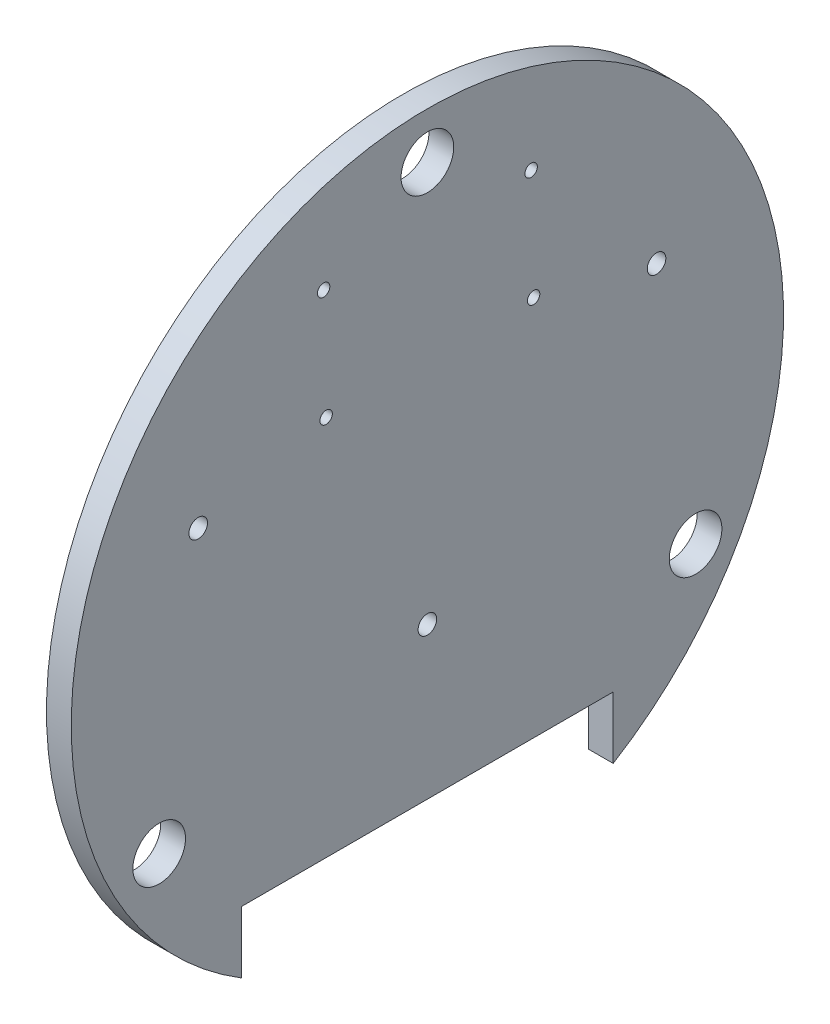
SolidWorks part; units mm, degrees
ref_plane "Ebene vorne" through (0, 0, 0) normal (0, 0, 1) x (1, 0, 0)
ref_plane "Ebene oben" through (0, 0, 0) normal (0, 1, 0) x (1, 0, 0)
ref_plane "Ebene rechts" through (0, 0, 0) normal (1, 0, 0) x (0, 0, -1)
sketch "Sketch1" plane through (0, 0, 0) normal (1, 0, 0) x (0, 0, -1)
  circle A0 centre (0, 0) radius 57.5
  dimension "D1" = 115
extrude "Boss-Extrude1" add sketch "Sketch1" along normal blind 4
sketch "Sketch2" plane through (0, 0, 0) normal (-1, 0, 0) x (0, 0, 1)
  circle A0 centre (0, 50) radius 4.25
  circle A1 centre (43.3013, -25) radius 4.25
  circle A2 centre (-43.3013, -25) radius 4.25
  point P9 (0, 0)
  dimension "D1" = 8.5
  dimension "D2" = 50
  dimension "D3" = 3
extrude "Cut-Extrude1" cut sketch "Sketch2" against normal through all
sketch "Sketch3" plane through (0, 0, 0) normal (-1, 0, 0) x (0, 0, 1)
  line L0 (-30, -49.0535) -> (-30, -39.0535)
  line L1 (0, 57.5) -> (0, -57.5) construction
  line L2 (30, -49.0535) -> (30, -39.0535)
  line L3 (-30, -39.0535) -> (30, -39.0535)
  circle A0 centre (0, 0) radius 57.5 construction
  arc A2 (-30, -49.0535) -> (30, -49.0535) centre (0, 0) ccw
  dimension "D1" = 10
  dimension "D2" = 60
extrude "Cut-Extrude2" cut sketch "Sketch3" against normal through all
sketch "Sketch4" plane through (4, 0, 0) normal (1, 0, 0) x (0, 0, -1)
  line L0 (0, 57.5) -> (0, -40.0081) construction
  circle A0 centre (-16.75, 40.5165) radius 1
  circle A1 centre (16.75, 40.5165) radius 1
  circle A2 centre (17.1527, 22.521) radius 1
  circle A3 centre (-16.3473, 22.521) radius 1
  circle A4 centre (-37, 17.3421) radius 1.5
  circle A5 centre (0, -14.613) radius 1.5
  circle A6 centre (37, 17.3421) radius 1.5
  arc A7 (30, -49.0535) -> (-30, -49.0535) centre (0, 0) ccw construction
  circle A8 centre (0, -14.613) radius 1.5 construction
  point P27 (0, 0)
  point P28 (0, 0)
  dimension "D1" = 2
  dimension "D2" = 3
extrude "Cut-Extrude3" cut sketch "Sketch4" against normal through all
